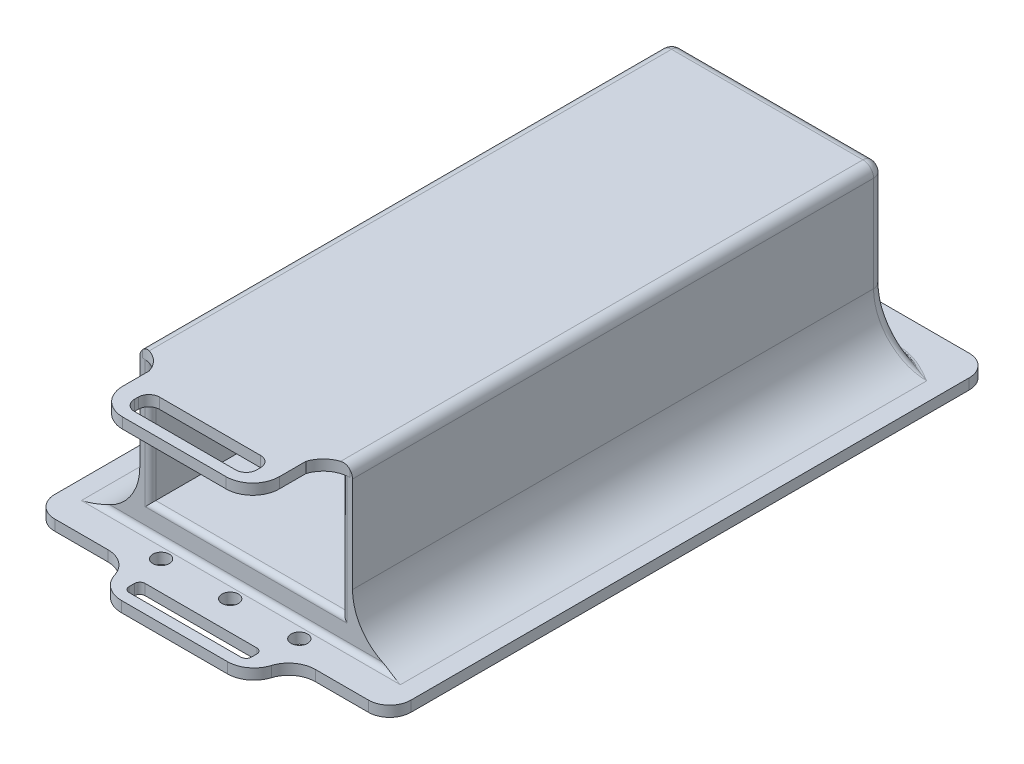
SolidWorks part; units mm, degrees
material "尼龙 101"
ref_plane "前视基准面" through (0, 0, 0) normal (0, 0, 1) x (1, 0, 0)
ref_plane "上视基准面" through (0, 0, 0) normal (0, 1, 0) x (1, 0, 0)
ref_plane "右视基准面" through (0, 0, 0) normal (1, 0, 0) x (0, 0, -1)
other "Configuration Table"
sketch "草图1" plane through (0, 0, 0) normal (0, 1, 0) x (1, 0, 0)
  line L0 (0, 56.5) -> (0, -56.5)
  line L1 (-29.5, 56.5) -> (29.5, 56.5)
  line L2 (-33.5, 52.5) -> (-33.5, -52.5)
  line L3 (-29.5, -56.5) -> (29.5, -56.5)
  line L4 (33.5, 52.5) -> (33.5, -52.5)
  line L5 (-33.5, 56.5) -> (33.5, -56.5) construction
  line L6 (-33.5, -56.5) -> (33.5, 56.5) construction
  line L7 (0, 53) -> (0, -53)
  line L8 (-13, -53) -> (13, -53)
  line L9 (-9, 53) -> (9, 53)
  arc A0 (-33.5, -52.5) -> (-29.5, -56.5) centre (-29.5, -52.5) ccw
  arc A1 (29.5, -56.5) -> (33.5, -52.5) centre (29.5, -52.5) ccw
  arc A2 (29.5, 56.5) -> (33.5, 52.5) centre (29.5, 52.5) cw
  arc A3 (-29.5, 56.5) -> (-33.5, 52.5) centre (-29.5, 52.5) ccw
  circle A4 centre (0, 53) radius 1.55
  circle A5 centre (0, -53) radius 1.55
  circle A6 centre (-13, -53) radius 1.55
  circle A7 centre (13, -53) radius 1.55
  circle A8 centre (-9, 53) radius 1.55
  circle A9 centre (9, 53) radius 1.55
  point P0 (0, 0)
  point P21 (0, 0)
  point P24 (0, 0)
  point P29 (0, -53)
  point P34 (0, 53)
  dimension "D3" = 4
  dimension "D5" = 3.1
  dimension "D6" = 3.1
  dimension "D8" = 3.1
  dimension "D9" = 3.1
  dimension "D11" = 3.1
  dimension "D12" = 3.1
  dimension "D1" = 113
  dimension "D2" = 67
  dimension "D4" = 106
  dimension "D7" = 26
  dimension "D10" = 18
extrude "凸台-拉伸1" add sketch "草图1" along normal blind 2 contours A9 A4 L7 A5 A7 L0 L3 A1 L4 A2 L1 | A8 A4 L0 L1 A3 L2 A0 L3 A5 A6 L7 region at (16.7765, 0, 0) region at (-16.7765, 0, 0)
sketch "草图3" plane through (0, 2, 0) normal (0, 1, 0) x (1, 0, 0)
  line L1 (-20, 50) -> (20, 50)
  line L2 (-20, 50) -> (-20, -50)
  line L3 (-20, -50) -> (20, -50)
  line L4 (20, 50) -> (20, -50)
  line L5 (-20, 50) -> (20, -50) construction
  line L6 (-20, -50) -> (20, 50) construction
  point P0 (0, 0)
  dimension "D1" = 100
  dimension "D2" = 40
extrude "凸台-拉伸2" add sketch "草图3" along normal blind 35
sketch "草图6" plane through (0, 0, 50) normal (0, 0, 1) x (1, 0, 0)
  line L0 (-20, 37) -> (-20, 2) construction
  line L1 (-18, 30) -> (18, 30)
  line L2 (-18, 30) -> (-18, 7)
  line L3 (-18, 7) -> (18, 7)
  line L4 (18, 30) -> (18, 7)
  line L5 (20, 37) -> (20, 2) construction
  line L6 (-29.5, 2) -> (29.5, 2) construction
  line L8 (-20, 37) -> (20, 37)
  line L9 (-20, 37) -> (-20, 32)
  line L10 (-20, 32) -> (20, 32)
  line L11 (20, 37) -> (20, 32)
  dimension "D1" = 2
  dimension "D2" = 2
  dimension "D3" = 5
  dimension "D4" = 36
  dimension "D5" = 23
  dimension "D6" = 2
extrude "切除-拉伸1" cut sketch "草图6" against normal blind 98
sketch "草图7" plane through (0, 0, -48) normal (0, 0, 1) x (1, 0, 0)
  line L1 (-20, 37) -> (20, 37)
  line L2 (-20, 37) -> (-20, 32)
  line L3 (-20, 32) -> (20, 32)
  line L4 (20, 37) -> (20, 32)
extrude "切除-拉伸2" cut sketch "草图7" against normal blind 98
sketch "草图8" plane through (0, 0, -50) normal (0, 0, -1) x (-1, 0, 0)
  line L0 (-20, 32) -> (-20, 2) construction
  line L1 (-9, 24) -> (9, 24)
  line L2 (-12, 21) -> (-12, 13)
  line L3 (-9, 10) -> (9, 10)
  line L4 (12, 21) -> (12, 13)
  line L5 (-12, 24) -> (12, 10) construction
  line L6 (-12, 10) -> (12, 24) construction
  line L7 (20, 32) -> (20, 2) construction
  line L8 (20, 32) -> (-20, 32) construction
  line L9 (-20, 2) -> (20, 2) construction
  arc A0 (-12, 13) -> (-9, 10) centre (-9, 13) ccw
  arc A1 (9, 10) -> (12, 13) centre (9, 13) ccw
  arc A2 (9, 24) -> (12, 21) centre (9, 21) cw
  arc A3 (-9, 24) -> (-12, 21) centre (-9, 21) ccw
  point P0 (0, 17)
  dimension "D5" = 3
  dimension "D1" = 8
  dimension "D2" = 8
  dimension "D3" = 8
  dimension "D4" = 8
extrude "切除-拉伸3" cut sketch "草图8" against normal blind 98
fillet "圆角1" radius 10 1 edges at (20, 2, 0)
fillet "圆角2" radius 10 1 edges at (-20, 2, 0)
fillet "圆角3" radius 2 1 edges at (20, 32, 0)
fillet "圆角4" radius 2 1 edges at (-20, 32, 0)
fillet "圆角5" radius 2 7 edges at (-22.9289, 4.9289, -50) (-20, 21, -50) (-19.4142, 31.4142, -50) (22.9289, 4.9289, -50) (20, 21, -50) (19.4142, 31.4142, -50) (0, 32, -50)
fillet "圆角7" radius 1 3 edges at (26.2498, 2, -49.5026) (-26.2498, 2, -49.5026) (0, 2, -50)
fillet "圆角8" radius 1 8 edges at (0, 24, -50) (-11.1213, 23.1213, -50) (-12, 17, -50) (-11.1213, 10.8787, -50) (0, 10, -50) (11.1213, 10.8787, -50) (12, 17, -50) (11.1213, 23.1213, -50)
fillet "圆角9" radius 1 1 edges at (0, 2, 50)
sketch "草图9" plane through (0, 0, 56.5) normal (0, 0, 1) x (1, 0, 0)
  line L0 (30, 2) -> (-30, 2) construction
  line L1 (-14.5, 2) -> (14.5, 2)
  line L2 (-14.5, 2) -> (-14.5, 0)
  line L3 (-14.5, 0) -> (14.5, 0)
  line L4 (14.5, 2) -> (14.5, 0)
  line L5 (-29.5, 0) -> (29.5, 0) construction
  line L6 (-29.5, 2) -> (-29.5, 0) construction
  line L7 (29.5, 2) -> (29.5, 0) construction
  point P10 (-29.5, 1)
  dimension "D1" = 15
  dimension "D2" = 15
  dimension "D3" = 29
extrude "凸台-拉伸4" add sketch "草图9" along normal blind 50
fillet "圆角10" radius 1 3 edges at (18, 18.5, 50) (-18, 18.5, 50) (0, 7, 50)
sketch "草图11" plane through (0, 0, 50) normal (0, 0, 1) x (1, 0, 0)
  line L1 (-18, 32) -> (18, 32) construction
  line L2 (-14.5, 32) -> (14.5, 32)
  line L3 (-14.5, 32) -> (-14.5, 30)
  line L4 (-14.5, 30) -> (14.5, 30)
  line L5 (14.5, 32) -> (14.5, 30)
  line L6 (18, 30) -> (-18, 30) construction
  line L7 (-20, 30) -> (-20, 12) construction
  line L9 (20, 30) -> (20, 12) construction
  dimension "D1" = 29
  dimension "D2" = 5.5
  dimension "D3" = 5.5
extrude "凸台-拉伸5" add sketch "草图11" along normal blind 50
sketch "草图12" plane through (0, 32, 0) normal (0, 1, 0) x (1, 0, 0)
  line L1 (-14.5, -50) -> (14.5, -50)
  line L2 (-14.5, -50) -> (-14.5, -100)
  line L3 (-14.5, -100) -> (14.5, -100)
  line L4 (14.5, -50) -> (14.5, -100)
  line L5 (-14.5, -100) -> (14.5, -100)
  line L6 (-14.5, -100) -> (-14.5, -60)
  line L7 (-14.5, -60) -> (14.5, -60)
  line L8 (14.5, -100) -> (14.5, -60)
  line M10 (-14.5, -100) -> (14.5, -100)
  line M11 (14.5, -100) -> (14.5, -50)
  dimension "D1" = 50
  dimension "D2" = 29
  dimension "D3" = 40
extrude "切除-拉伸4" cut sketch "草图12" against normal blind 10 contours L7 L2 M10 M11 region at (0, 32, 80)
sketch "草图13" plane through (0, 32, 0) normal (0, 1, 0) x (1, 0, 0)
  line L1 (-11.5, -52) -> (11.5, -52)
  line L2 (-11.5, -52) -> (-11.5, -55)
  line L3 (-11.5, -55) -> (11.5, -55)
  line L4 (11.5, -52) -> (11.5, -55)
  line L6 (-14.5, -60) -> (-14.5, -50) construction
  line L7 (14.5, -60) -> (14.5, -50) construction
  line L8 (-18, -50) -> (-14.5, -50) construction
  dimension "D1" = 3
  dimension "D2" = 3
  dimension "D3" = 2
  dimension "D4" = 3
extrude "切除-拉伸5" cut sketch "草图13" against normal blind 10
sketch "草图14" plane through (0, 32, 0) normal (0, 1, 0) x (1, 0, 0)
  line L0 (-14.5, -60) -> (-14.5, -50) construction
  line L1 (-14.5, -57) -> (14.5, -57)
  line L2 (-14.5, -57) -> (-14.5, -60)
  line L3 (-14.5, -60) -> (14.5, -60)
  line L4 (14.5, -57) -> (14.5, -60)
  line L5 (-11.5, -55) -> (11.5, -55) construction
  dimension "D1" = 2
extrude "切除-拉伸6" cut sketch "草图14" against normal blind 10
fillet "圆角11" radius 5 2 edges at (14.5, 31, 50) (-14.5, 31, 50)
fillet "圆角12" radius 1 4 edges at (-11.5, 31, 55) (11.5, 31, 55) (11.5, 31, 52) (-11.5, 31, 52)
fillet "圆角13" radius 5 2 edges at (14.5, 1, 56.5) (-14.5, 1, 56.5)
sketch "草图15" plane through (0, 2, 0) normal (0, 1, 0) x (1, 0, 0)
  line L0 (-29.5, -56.5) -> (29.5, -56.5)
  line L1 (14.5, -106.5) -> (14.5, -61.5) construction
  line L2 (-14.5, -56.5) -> (14.5, -56.5)
  line L3 (-14.5, -56.5) -> (-14.5, -63.5)
  line L4 (-14.5, -63.5) -> (14.5, -63.5)
  line L5 (14.5, -56.5) -> (14.5, -63.5)
  line L9 (-11.5, -58.5) -> (11.5, -58.5)
  line L10 (-11.5, -58.5) -> (-11.5, -61.5)
  line L11 (-11.5, -61.5) -> (11.5, -61.5)
  line L12 (11.5, -58.5) -> (11.5, -61.5)
  line M19 (-14.5, -61.5) -> (-14.5, -106.5)
  line M20 (-14.5, -106.5) -> (14.5, -106.5)
  line M21 (14.5, -106.5) -> (14.5, -61.5)
  dimension "D1" = 7
  dimension "D2" = 23
  dimension "D3" = 3
  dimension "D4" = 3
  dimension "D5" = 3
  dimension "D6" = 2
  dimension "D7" = 2
extrude "切除-拉伸7" cut sketch "草图15" against normal blind 10 contours L12 L9 L10 L11 | L4 M19 M20 M21 region at (0, 2, 85) region at (0, 2, 60)
fillet "圆角14" radius 5 2 edges at (14.5, 1, 63.5) (-14.5, 1, 63.5)
fillet "圆角15" radius 1 4 edges at (11.5, 1, 58.5) (-11.5, 1, 61.5) (11.5, 1, 61.5) (-11.5, 1, 58.5)
fillet "圆角16" radius 5 2 edges at (14.5, 31, 57) (-14.5, 31, 57)
sketch "草图17" plane through (0, 32, 0) normal (0, 1, 0) x (1, 0, 0)
  line L0 (-14.7303, -53.5) -> (14.7303, -53.5)
  line L1 (14.7303, -53.5) -> (14.7303, -63.5)
  line L2 (14.7303, -63.5) -> (-14.7303, -63.5)
  line L3 (-14.7303, -63.5) -> (-14.7303, -53.5)
  line L5 (-14.7303, -53.5) -> (14.7303, -53.5)
  line L6 (-14.7303, -53.5) -> (-14.7303, -50.9376)
  line L7 (-14.7303, -50.9376) -> (14.7303, -50.9376)
  line L8 (14.7303, -53.5) -> (14.7303, -50.9376)
  line M1 (10.5, -55) -> (-10.5, -55)
  arc M2 (-10.5, -55) -> (-11.5, -54) centre (-10.5, -54) cw
  line M3 (-11.5, -54) -> (-11.5, -53)
  arc M4 (-11.5, -53) -> (-10.5, -52) centre (-10.5, -53) cw
  line M5 (-10.5, -52) -> (10.5, -52)
  arc M6 (10.5, -52) -> (11.5, -53) centre (10.5, -53) cw
  line M7 (11.5, -53) -> (11.5, -54)
  arc M8 (11.5, -54) -> (10.5, -55) centre (10.5, -54) cw
  line M9 (-9.9606, -57) -> (9.9606, -57)
  arc M10 (9.9606, -57) -> (14.7303, -53.5) centre (9.9606, -52) ccw
  arc M16 (-14.7303, -53.5) -> (-9.9606, -57) centre (-9.9606, -52) ccw
extrude "凸台-拉伸6" add sketch "草图17" against normal blind 2 contours L3 L2 L1 M10 M9 M16 | L0 L8 L7 L6 M3 M4 M5 M6 M7 | L0 M3 M7 M6 M5 M4 | L0 M3 M2 M1 M8 M7 | L0 M16 M9 M10 M7 M8 M1 M2 M3 region at (0, 32, 51.7764) region at (0, 32, 60.0645) region at (0, 32, 55.6992) region at (0, 32, 52.7566) region at (0, 32, 54.2434)
sketch "草图18" plane through (0, 30, 0) normal (0, -1, 0) x (1, 0, 0)
  line L1 (-11.5, 61.5) -> (11.5, 61.5)
  line L2 (-11.5, 61.5) -> (-11.5, 58.5)
  line L3 (-11.5, 58.5) -> (11.5, 58.5)
  line L4 (11.5, 61.5) -> (11.5, 58.5)
extrude "切除-拉伸8" cut sketch "草图18" against normal blind 2
fillet "圆角17" radius 2 2 edges at (11.5, 31, 61.5) (-11.5, 31, 61.5)
fillet "圆角18" radius 5 2 edges at (14.7303, 31, 63.5) (-14.7303, 31, 63.5)
sketch "草图19" plane through (0, 32, 0) normal (0, 1, 0) x (1, 0, 0)
  line L0 (-11.5, -58.7436) -> (11.5, -58.7436)
  line L1 (-11.5, -59.5) -> (-11.5, -58.5) construction
  line L2 (11.5, -58.5) -> (11.5, -59.5) construction
  line L3 (11.5, -58.7436) -> (11.5, -56.7923)
  line L4 (11.5, -56.7923) -> (-11.5, -56.7923)
  line L5 (-11.5, -56.7923) -> (-11.5, -58.7436)
extrude "切除-拉伸9" cut sketch "草图19" against normal blind 2
fillet "圆角19" radius 2 2 edges at (11.5, 31, 56.7923) (-11.5, 31, 56.7923)
